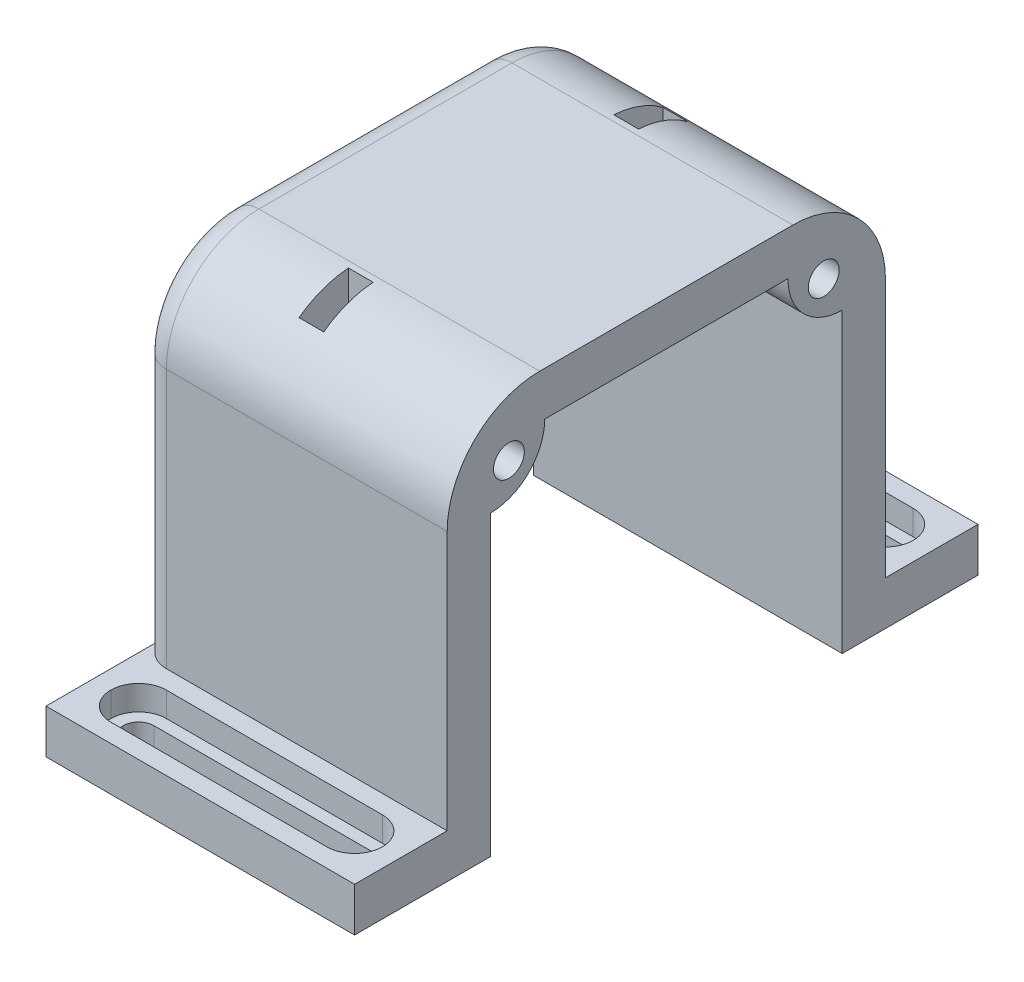
SolidWorks part; units mm, degrees
ref_plane "Front Plane" through (0, 0, 0) normal (0, 0, 1) x (1, 0, 0)
ref_plane "Top Plane" through (0, 0, 0) normal (0, 1, 0) x (1, 0, 0)
ref_plane "Right Plane" through (0, 0, 0) normal (1, 0, 0) x (0, 0, -1)
sketch "Sketch1" plane through (0, 0, 0) normal (1, 0, 0) x (0, 0, -1)
  line L5 (-28.5, 28.5) -> (28.5, -28.5) construction
  line L6 (-28.5, -28.5) -> (28.5, 28.5) construction
  line L7 (35.5, 35.6293) -> (-35.5, 35.6293)
  line L8 (-35.5, 35.6293) -> (-35.5, -21.3707)
  line L9 (-35.5, -21.3707) -> (-50.5, -21.3707)
  line L10 (-50.5, -21.3707) -> (-50.5, -28.5)
  line L11 (-50.5, -28.5) -> (-28.5, -28.5)
  line L12 (-28.5, -28.5) -> (-28.5, 19.7)
  line L13 (19.7, 28.5) -> (-19.7, 28.5)
  line L14 (50.5, -21.3707) -> (50.5, -28.5)
  line L15 (35.5, -21.3707) -> (50.5, -21.3707)
  line L16 (35.5, 35.6293) -> (35.5, -21.3707)
  line L17 (28.5, -28.5) -> (28.5, 19.7)
  line L18 (50.5, -28.5) -> (28.5, -28.5)
  arc A1 (-28.5, 19.7) -> (-19.7, 28.5) centre (-28.5, 28.5) ccw
  arc A2 (28.5, 19.7) -> (19.7, 28.5) centre (28.5, 28.5) cw
  point P0 (0, 0)
  dimension "D5" = 15
  dimension "D1" = 57
  dimension "D2" = 57
extrude "Boss-Extrude1" add sketch "Sketch1" along normal blind 50
sketch "Sketch2" plane through (0, 0, 0) normal (-1, 0, 0) x (0, 0, 1)
  line L0 (-35.5, 35.6293) -> (0, 0) construction
  line L1 (-28.5, 19.7) -> (-28.5, -28.5) construction
  line L2 (0, 42.4806) -> (0, -25.1676) construction
  line L3 (-35.5, -21.3707) -> (-35.5, 35.6293) construction
  circle A0 centre (-25.5, 25.5929) radius 2.5
  circle A2 centre (25.5, 25.5929) radius 2.5
  dimension "D1" = 5
  dimension "D2" = 3
  dimension "D3" = 10
extrude "Cut-Extrude1" cut sketch "Sketch2" against normal blind 50
fillet "Fillet1" radius 15 2 edges at (25, 35.6293, 35.5) (25, 35.6293, -35.5)
sketch "Sketch3" plane through (0, 35.6293, 0) normal (0, 1, 0) x (1, 0, 0)
  line L1 (20, 29.5) -> (24, 29.5)
  line L2 (20, 29.5) -> (20, 21.5)
  line L3 (20, 21.5) -> (24, 21.5)
  line L4 (24, 29.5) -> (24, 21.5)
  line L5 (-4.4176, 0) -> (51.6177, 0) construction
  line L6 (20, -21.5) -> (24, -21.5)
  line L7 (24, -29.5) -> (24, -21.5)
  line L8 (20, -29.5) -> (24, -29.5)
  line L17 (20, -29.5) -> (20, -21.5)
  dimension "D1" = 8
  dimension "D2" = 4
extrude "Cut-Extrude2" cut sketch "Sketch3" against normal blind 14.54
sketch "Sketch4" plane through (0, -21.3707, 0) normal (0, 1, 0) x (1, 0, 0)
  line L6 (0, -35.5) -> (50, -50.5) construction
  line L7 (50, -35.5) -> (0, -50.5) construction
  line L9 (3, -38.5) -> (47, -38.5)
  line L10 (3, -38.5) -> (3, -47.5)
  line L11 (3, -47.5) -> (47, -47.5)
  line L12 (47, -38.5) -> (47, -47.5)
  line L13 (3, -38.5) -> (47, -47.5) construction
  line L14 (3, -47.5) -> (47, -38.5) construction
  line L15 (50, -35.5) -> (50, -50.5) construction
  line L16 (-1.8281, 0) -> (54.8376, 0) construction
  line L17 (3, 47.5) -> (47, 47.5)
  line L18 (47, 38.5) -> (47, 47.5)
  line L19 (3, 38.5) -> (47, 38.5)
  line L20 (3, 38.5) -> (3, 47.5)
  point P4 (25, -43)
  dimension "D1" = 9
  dimension "D2" = 3
extrude "Cut-Extrude3" cut sketch "Sketch4" against normal blind 4
sketch "Sketch5" plane through (0, -25.3707, 0) normal (0, 1, 0) x (1, 0, 0)
  line L0 (3, -38.5) -> (47, -47.5) construction
  line L1 (47, -47.5) -> (47, -38.5) construction
  line L2 (47, -38.5) -> (3, -47.5) construction
  line L4 (5, -40.5) -> (45, -40.5)
  line L5 (5, -40.5) -> (5, -45.5)
  line L6 (5, -45.5) -> (45, -45.5)
  line L7 (45, -40.5) -> (45, -45.5)
  line L8 (5, -40.5) -> (45, -45.5) construction
  line L9 (5, -45.5) -> (45, -40.5) construction
  line L10 (3, -38.5) -> (3, -47.5) construction
  line L11 (-1.2266, 0) -> (55.9736, 0) construction
  line L12 (5, 45.5) -> (45, 45.5)
  line L13 (45, 40.5) -> (45, 45.5)
  line L14 (5, 40.5) -> (45, 40.5)
  line L15 (5, 40.5) -> (5, 45.5)
  point P4 (25, -43)
  dimension "D1" = 5
  dimension "D2" = 2
extrude "Cut-Extrude4" cut sketch "Sketch5" against normal through all
fillet "Fillet2" radius 2.5 8 edges at (45, -26.9353, 40.5) (45, -26.9353, 45.5) (5, -26.9353, 45.5) (5, -26.9353, 40.5) (5, -26.9353, -45.5) (5, -26.9353, -40.5) (45, -26.9353, -45.5) (45, -26.9353, -40.5)
fillet "Fillet3" radius 4.5 8 edges at (3, -23.3707, 38.5) (3, -23.3707, 47.5) (47, -23.3707, 47.5) (47, -23.3707, 38.5) (47, -23.3707, -47.5) (47, -23.3707, -38.5) (3, -23.3707, -47.5) (3, -23.3707, -38.5)
fillet "Fillet4" radius 4.5 5 edges at (0, -0.3707, -35.5) (0, 31.2359, -31.1066) (0, -0.3707, 35.5) (0, 31.2359, 31.1066) (0, 35.6293, 0)
